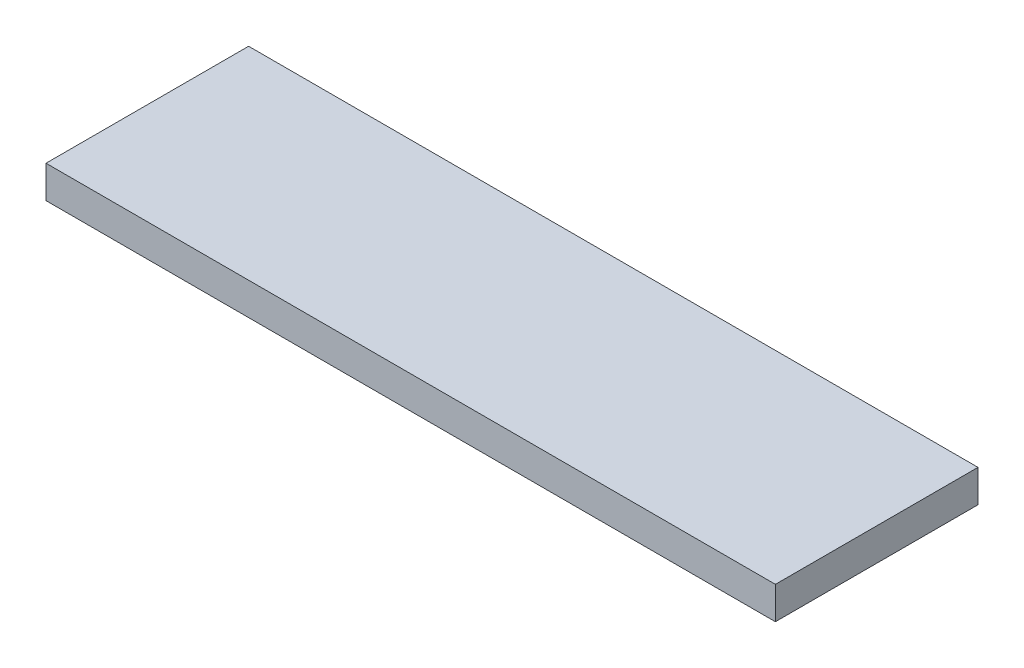
SolidWorks part; units mm, degrees
ref_plane "Front Plane" through (0, 0, 0) normal (0, 0, 1) x (1, 0, 0)
ref_plane "Top Plane" through (0, 0, 0) normal (0, 1, 0) x (1, 0, 0)
ref_plane "Right Plane" through (0, 0, 0) normal (1, 0, 0) x (0, 0, -1)
sketch "Sketch1" plane through (0, 0, 0) normal (0, 1, 0) x (1, 0, 0)
  line L1 (0, 0) -> (45, 0)
  line L2 (0, 0) -> (0, 12.5)
  line L3 (0, 12.5) -> (45, 12.5)
  line L4 (45, 0) -> (45, 12.5)
  dimension "D1" = 12.5
  dimension "D2" = 45
extrude "Boss-Extrude1" add sketch "Sketch1" along normal blind 2
sketch "Sketch2" plane through (0, 0, -12.5) normal (0, 0, -1) x (-1, 0, 0)
  line L1 (-45, 2) -> (0, 2)
  line L2 (-45, 2) -> (-45, 39)
  line L3 (-45, 39) -> (0, 39)
  line L4 (0, 2) -> (0, 39)
  dimension "D1" = 37
